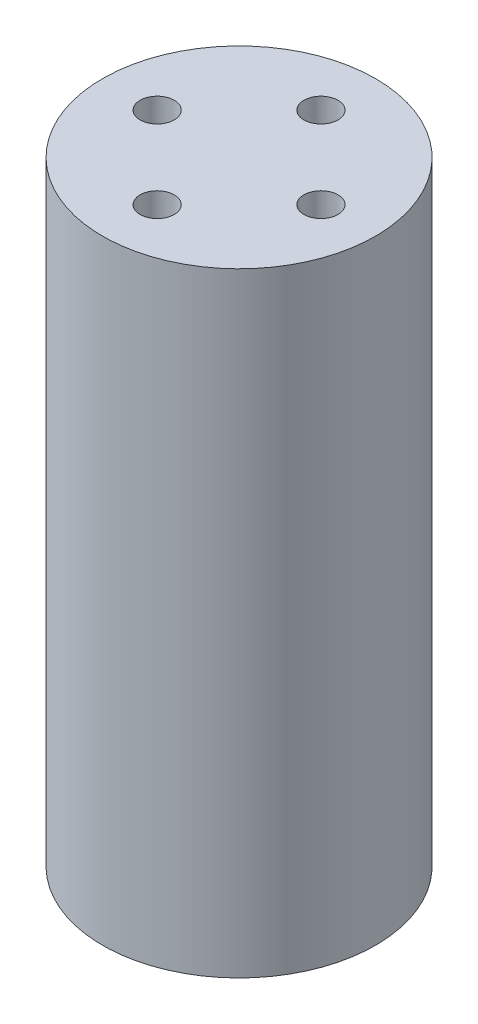
SolidWorks part; units mm, degrees
ref_plane "Спереди" through (0, 0, 0) normal (0, 0, 1) x (1, 0, 0)
ref_plane "Сверху" through (0, 0, 0) normal (0, 1, 0) x (1, 0, 0)
ref_plane "Справа" through (0, 0, 0) normal (1, 0, 0) x (0, 0, -1)
sketch "Эскиз1" plane through (0, 0, 0) normal (0, 1, 0) x (1, 0, 0)
  circle A0 centre (0, 0) radius 10
  dimension "D1" = 20
extrude "Бобышка-Вытянуть1" add sketch "Эскиз1" along normal blind 45
sketch "Эскиз2" plane through (0, 45, 0) normal (0, 1, 0) x (1, 0, 0)
  line L0 (0, 10) -> (0, -10) construction
  line L1 (10, 0) -> (-10, 0) construction
  circle A0 centre (0, 0) radius 10 construction
  circle A1 centre (0, 0) radius 6 construction
  dimension "D1" = 12
hole_wizard "Отверстие обработанное метчиком M3x0.51" positions "Эскиз4" profile "Эскиз3" tap size "M3x0.5" standard "Ansi Metric"
sketch "Эскиз4" plane through (0, 45, 0) normal (0, 1, 0) x (1, 0, 0)
  line L0 (0, 10) -> (0, -10) construction
  line L1 (10, 0) -> (-10, 0) construction
  circle A0 centre (0, 0) radius 6 construction
  point P0 (0, 6)
  point P6 (-6, 0)
  point P10 (0, -6)
  point P12 (6, 0)
sketch "Эскиз3" plane through (0, 45, -6) normal (1, 0, 0) x (0, 0, 1)
  line L0 (0, 0) -> (0, 9.2511)
  line L1 (0, 9.2511) -> (1.25, 8.5)
  line L2 (1.25, 8.5) -> (1.25, 0)
  line L5 (1.25, 0) -> (0, 0)
  line L10 (0, 9.2511) -> (-1.25, 8.5) construction
  line L11 (0, -6.35) -> (0, 107.95) construction
  dimension "Диаметр сверла" = 2.5
  dimension "Глубина сверла" = 8.5
  dimension "Угол заточки сверла" = 118
sketch "Эскиз5" plane through (0, 0, 0) normal (0, -1, 0) x (1, 0, 0)
  line L0 (0, 10) -> (0, -10) construction
  line L1 (10, 0) -> (-10, 0) construction
  circle A1 centre (0, 0) radius 6 construction
  circle A2 centre (0, 0) radius 10 construction
  dimension "D1" = 12
hole_wizard "Отверстие обработанное метчиком M3x0.52" positions "Эскиз7" profile "Эскиз6" tap size "M3x0.5" standard "Ansi Metric"
sketch "Эскиз7" plane through (0, 0, 0) normal (0, -1, 0) x (-1, 0, 0)
  line L0 (0, 10) -> (0, -10) construction
  line L1 (-10, 0) -> (10, 0) construction
  circle A0 centre (0, 0) radius 6 construction
  point P0 (0, 6)
  point P6 (-6, 0)
  point P10 (0, -6)
  point P12 (6, 0)
sketch "Эскиз6" plane through (0, 0, -6) normal (1, 0, 0) x (0, 0, -1)
  line L0 (0, 0) -> (0, 9.2511)
  line L1 (0, 9.2511) -> (1.25, 8.5)
  line L2 (1.25, 8.5) -> (1.25, 0)
  line L5 (1.25, 0) -> (0, 0)
  line L10 (0, 9.2511) -> (-1.25, 8.5) construction
  line L11 (0, -6.35) -> (0, 107.95) construction
  dimension "Диаметр сверла" = 2.5
  dimension "Глубина сверла" = 8.5
  dimension "Угол заточки сверла" = 118
